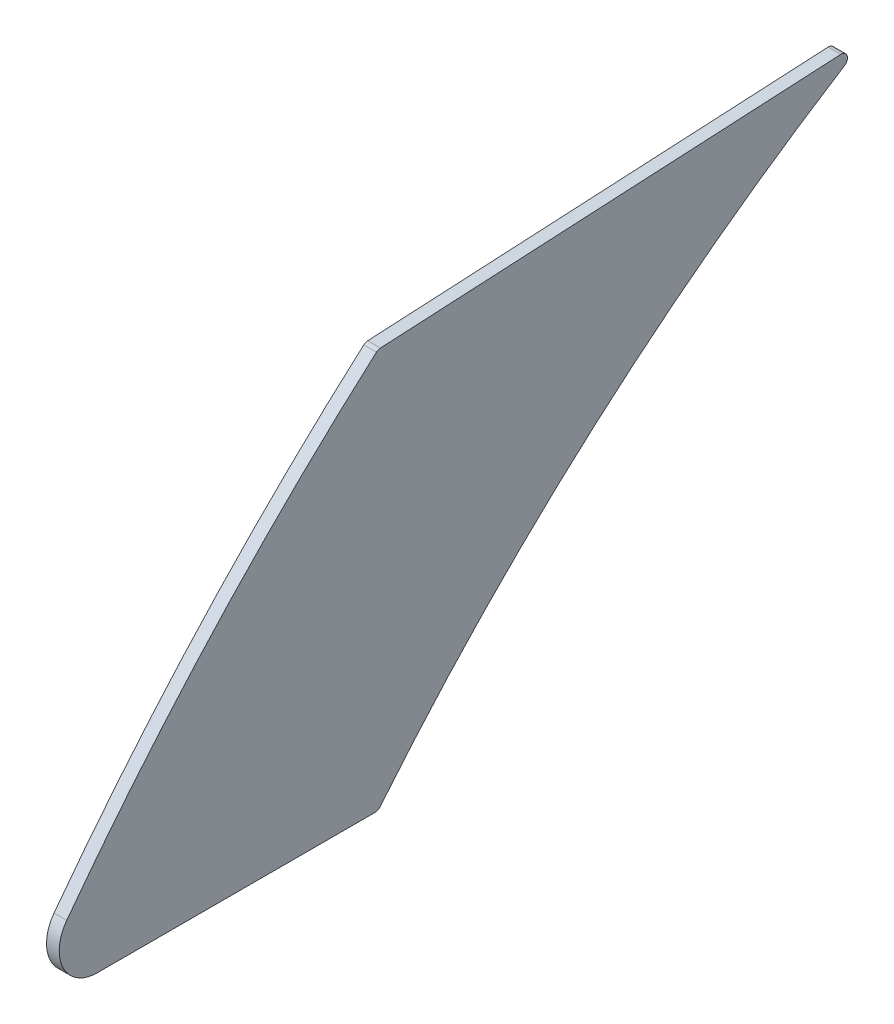
SolidWorks part; units mm, degrees
ref_plane "Front Plane" through (0, 0, 0) normal (0, 0, 1) x (1, 0, 0)
ref_plane "Top Plane" through (0, 0, 0) normal (0, 1, 0) x (1, 0, 0)
ref_plane "Right Plane" through (0, 0, 0) normal (1, 0, 0) x (0, 0, -1)
sketch "Sketch1" plane through (0, 0, 0) normal (1, 0, 0) x (0, 0, -1)
  line L0 (0.3485, 0.0183) -> (72.9858, 3.825)
  line L1 (-44.3055, -63) -> (-0.4751, -63)
  arc A0 (0.2996, -62.6323) -> (73.5686, 1.9787) centre (232.7073, -252.3339) cw
  arc A1 (-49.1194, -53.4186) -> (-0.2619, -0.2315) centre (231.6898, -262.3354) cw
  arc A2 (-44.3055, -63) -> (-49.1194, -53.4186) centre (-44.3055, -57) cw
  arc A3 (-0.4751, -63) -> (0.2996, -62.6323) centre (-0.4751, -62) ccw
  arc A4 (0.3485, 0.0183) -> (-0.2619, -0.2315) centre (0.4009, -0.9804) ccw
  arc A5 (72.9858, 3.825) -> (73.5686, 1.9787) centre (73.0381, 2.8264) cw
  point P9 (-56, -63)
  point P10 (77, 0)
  point P11 (76.8699, 4.4736)
  point P12 (0, 0)
  point P15 (0, -63)
  point P18 (0, 0)
  point P21 (76.8945, 4.0299)
  dimension "D5" = 350
  dimension "D6" = 300
  dimension "D7" = 6
  dimension "D4" = 1
  dimension "D1" = 77
  dimension "D2" = 63
  dimension "D3" = 56
  dimension "D8" = 3
extrude "Boss-Extrude1" add sketch "Sketch1" along normal blind 2
